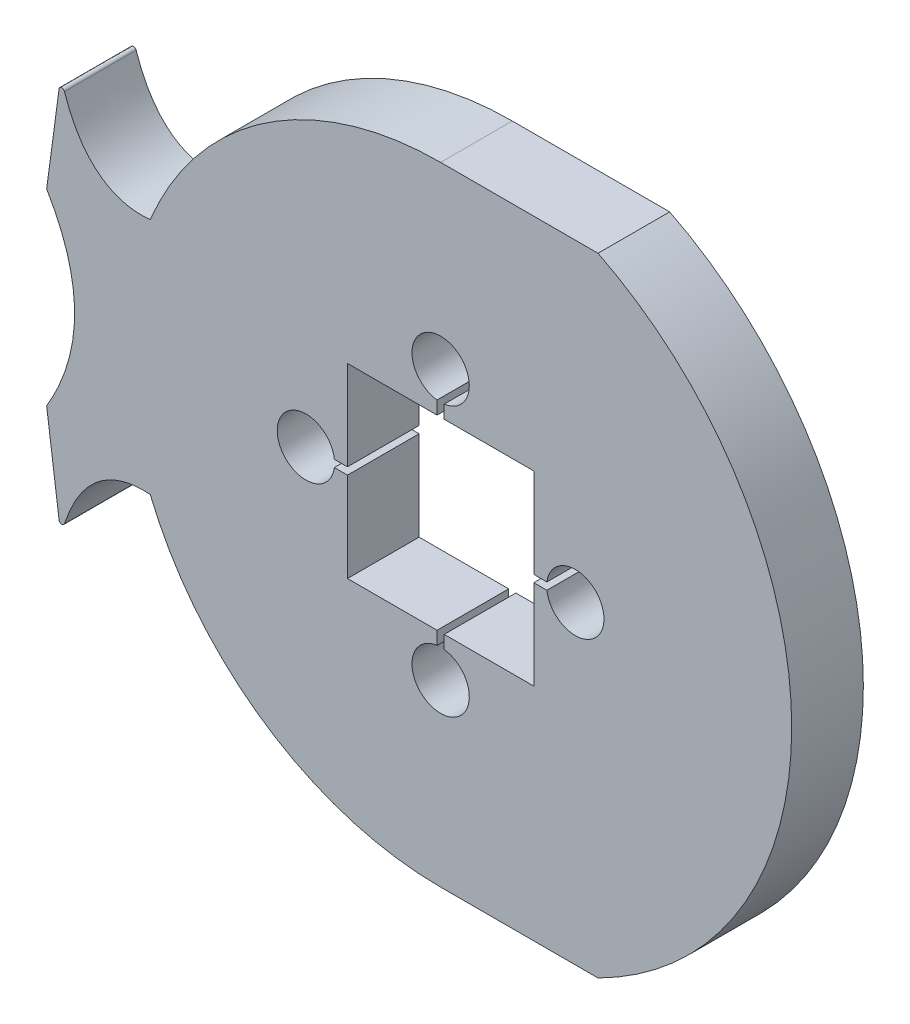
SolidWorks part; units mm, degrees
material "AISI 1020"
ref_plane "Front Plane" through (0, 0, 0) normal (0, 0, 1) x (1, 0, 0)
ref_plane "Top Plane" through (0, 0, 0) normal (0, 1, 0) x (1, 0, 0)
ref_plane "Right Plane" through (0, 0, 0) normal (1, 0, 0) x (0, 0, -1)
other "Center of Mass"
sketch "Sketch1" plane through (0, 0, 0) normal (0, 0, 1) x (1, 0, 0)
  line L0 (-11.938, 0) -> (0, 0) construction
  line L1 (-8.255, 8.255) -> (8.255, 8.255)
  line L2 (-8.255, 8.255) -> (-8.255, -8.255)
  line L3 (-8.255, -8.255) -> (8.255, -8.255)
  line L4 (8.255, 8.255) -> (8.255, -8.255)
  line L5 (0, 0) -> (0, 11.938) construction
  line L6 (11.938, 0) -> (0, 0) construction
  line L7 (0, 0) -> (0, -11.938) construction
  line L9 (-9.4179, 0.3175) -> (9.4179, 0.3175)
  line L10 (-9.4179, 0.3175) -> (-9.4179, -0.3175)
  line L11 (-9.4179, -0.3175) -> (9.4179, -0.3175)
  line L12 (9.4179, 0.3175) -> (9.4179, -0.3175)
  line L13 (-0.3175, 9.4179) -> (0.3175, 9.4179)
  line L14 (-0.3175, 9.4179) -> (-0.3175, -9.4179)
  line L15 (-0.3175, -9.4179) -> (0.3175, -9.4179)
  line L16 (0.3175, 9.4179) -> (0.3175, -9.4179)
  line L17 (0, 27.813) -> (13.9492, 27.813)
  line L18 (0, -27.813) -> (13.9492, -27.813)
  line L19 (-33.8048, 16.6086) -> (-34.9172, 8.3198)
  line L20 (-34.9172, -8.3198) -> (-33.8048, -16.6086)
  circle A1 centre (0, 11.938) radius 2.54
  circle A2 centre (0, -11.938) radius 2.54
  circle A3 centre (11.938, 0) radius 2.54
  circle A4 centre (-11.938, 0) radius 2.54
  arc A36 (8.7964, -10.0222) -> (10.0222, -8.7964) centre (0, 0) ccw
  arc A37 (-25.7359, -10.5464) -> (0, -27.813) centre (0, 0) ccw
  arc A39 (-33.3353, 16.5776) -> (-33.8048, 16.6086) centre (-33.5763, 16.4976) ccw
  arc A40 (-33.3353, -16.5776) -> (-33.8048, -16.6086) centre (-33.5763, -16.4976) cw
  arc A41 (13.9492, -27.813) -> (13.9492, 27.813) centre (0, 0) ccw
  arc A42 (0, 27.813) -> (-25.7359, 10.5464) centre (0, 0) ccw
  spline S0 degree 3 poles (-33.3353, 16.5776) (-31.8977, 12.2441) (-29.218, 10.1877) (-25.7359, 10.5464) knots 0.081541 0.081541 0.081541 0.081541 1 1 1 1
  spline S1 degree 3 poles (-33.3353, -16.5776) (-31.8977, -12.2441) (-29.2304, -10.2896) (-25.7359, -10.5464) knots 0.081541 0.081541 0.081541 0.081541 1 1 1 1
  spline S2 degree 2 poles (-34.9172, 8.3198) (-29.9564, 0) (-34.9172, -8.3198) knots 0 0 0 1 1 1
  point P7 (8.255, 0)
  point P8 (0, 8.255)
  point P27 (0, 0)
  point P54 (0, 0)
  point P70 (0, 0)
  point P77 (0, 0)
  dimension "D4" = 5.08
  dimension "D10" = 55.626
  dimension "D12" = 0.254
  dimension "D14" = 62.23
  dimension "D1" = 16.51
  dimension "D3" = 11.938
  dimension "D5" = 0.635
extrude "Boss-Extrude1" add sketch "Sketch1" along normal blind 6.35 contours A4 L9 L2 L1 L14 A1 L16 L4 A3 L11 L3 A2 region at (6.9746, 26.9496, 0)
